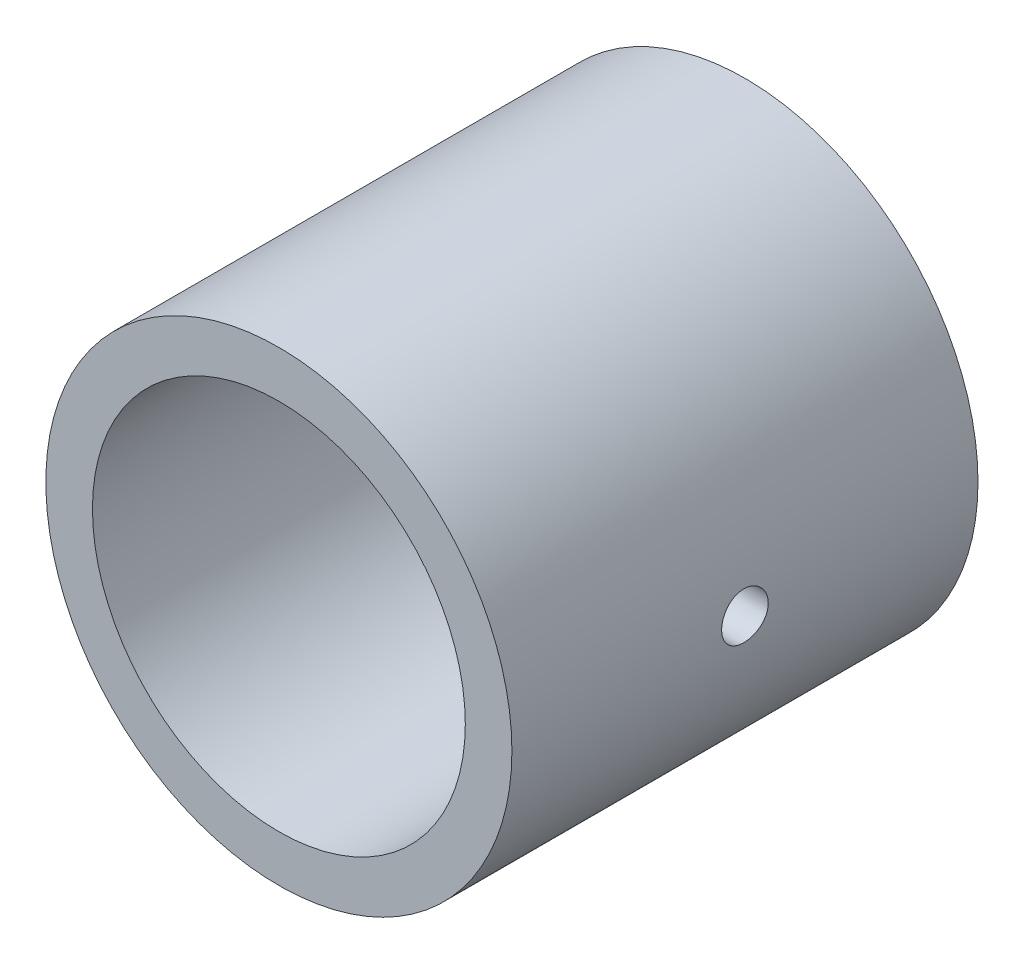
SolidWorks part; units mm, degrees
ref_plane "Front Plane" through (0, 0, 0) normal (0, 0, 1) x (1, 0, 0)
ref_plane "Top Plane" through (0, 0, 0) normal (0, 1, 0) x (1, 0, 0)
ref_plane "Right Plane" through (0, 0, 0) normal (1, 0, 0) x (0, 0, -1)
sketch "Sketch1" plane through (0, 0, 0) normal (0, 0, 1) x (1, 0, 0)
  circle A0 centre (0, 0) radius 25
  dimension "D1" = 50
extrude "Boss-Extrude1" add sketch "Sketch1" along normal blind 50
sketch "Sketch2" plane through (0, 0, 50) normal (0, 0, 1) x (1, 0, 0)
  circle A0 centre (0, 0) radius 20
  dimension "D1" = 40
extrude "Cut-Extrude1" cut sketch "Sketch2" against normal blind 50
sketch "Sketch3" plane through (0, 0, 0) normal (1, 0, 0) x (0, 0, -1)
  circle A0 centre (-25, 0) radius 2.5
  dimension "D2" = 5
extrude "Cut-Extrude2" cut sketch "Sketch3" against normal blind 50 and the other way blind 50
